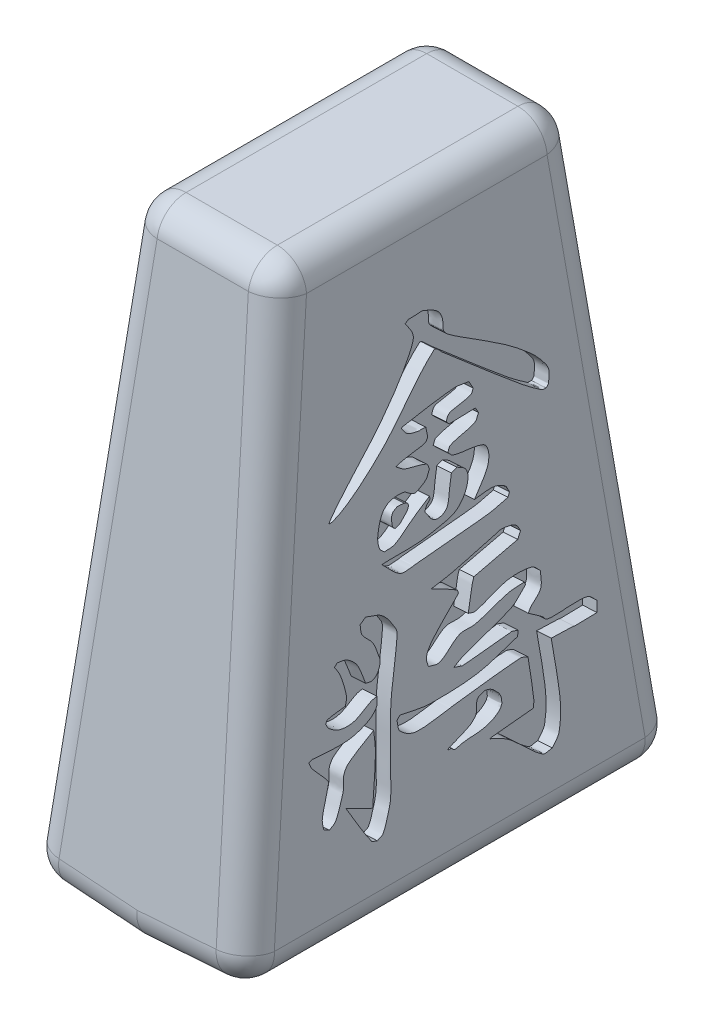
SolidWorks part; units mm, degrees
ref_plane "Płaszczyzna przednia" through (0, 0, 0) normal (0, 0, 1) x (1, 0, 0)
ref_plane "Płaszczyzna górna" through (0, 0, 0) normal (0, 1, 0) x (1, 0, 0)
ref_plane "Płaszczyzna prawa" through (0, 0, 0) normal (1, 0, 0) x (0, 0, -1)
sketch "Szkic1" plane through (0, 0, 0) normal (0, 0, 1) x (1, 0, 0)
  line L0 (0, 0) -> (0, 40)
  line L1 (3.1225, 40) -> (-3.1225, 40)
  line L2 (-5.1185, 38.1262) -> (-7.3738, 2.4704)
  line L3 (-5.504, 0.3481) -> (0, 0)
  line L4 (5.504, 0.3481) -> (0, 0)
  line L5 (5.1185, 38.1262) -> (7.3738, 2.4704)
  arc A0 (-3.1225, 40) -> (-5.1185, 38.1262) centre (-3.1225, 38) ccw
  arc A1 (-7.3738, 2.4704) -> (-5.504, 0.3481) centre (-5.3777, 2.3441) ccw
  arc A2 (7.3738, 2.4704) -> (5.504, 0.3481) centre (5.3777, 2.3441) cw
  arc A3 (3.1225, 40) -> (5.1185, 38.1262) centre (3.1225, 38) cw
  point P7 (-5, 40)
  point P10 (-7.5, 0.4744)
  point P17 (7.5, 0.4744)
  point P18 (5, 40)
  dimension "D5" = 2
  dimension "D1" = 40
  dimension "D2" = 90
  dimension "D3" = 5
  dimension "D4" = 7.5
extrude "Dodanie-wyciągnięcie1" add sketch "Szkic1" along normal blind 30 contours L2 A1 L3 L0 L1 A0 | A3 L1 L0 L4 A2 L5 region at (-3.1441, 18.7866, 0) region at (3.1441, 18.7866, 0)
ref_plane "Płaszczyzna1" through (5.1225, 0, 0) normal (1, 0, 0) x (0, 0, -1)
ref_plane "Płaszczyzna2" through (15.1225, 0, 0) normal (1, 0, 0) x (0, 0, -1)
sketch "Szkic7" plane through (15.1225, 0, 0) normal (1, 0, 0) x (0, 0, -1)
  line L0 (-25, 40) -> (-5, 40)
  line L1 (-30, 40) -> (0, 40) construction
  line L2 (-5, 40) -> (0, 0)
  line L3 (0, 0) -> (-30, 0)
  line L4 (-30, 0) -> (0, 0) construction
  line L5 (-15, 0) -> (-15, 40)
  line L6 (-25, 40) -> (-30, 0)
  line L8 (0, 0) -> (-30, 0)
  line L9 (0, 0) -> (0, 40)
  line L10 (0, 40) -> (-30, 40)
  line L11 (-30, 0) -> (-30, 40)
  dimension "D1" = 10
  dimension "D2" = 15
  dimension "D3" = 40
extrude "Wytnij-wyciągnięcie11" cut sketch "Szkic7" against normal through all and the other way through all contours L11 L6 L10 | L9 L10 L2 region at (15.1225, 26.6667, 28.3333) region at (15.1225, 26.6667, 1.6667)
fillet "Zaokrąglenie2" radius 2 18 edges at (0, 40, 5) (-4.4914, 39.4582, 4.9323) (-6.2461, 20.2983, 2.5373) (-6.8784, 1.022, 0.1278) (-2.752, 0.1741, 0.0218) (2.752, 0.1741, 0.0218) (6.8784, 1.022, 0.1278) (6.2461, 20.2983, 2.5373) (4.4914, 39.4582, 4.9323) (4.4914, 39.4582, 25.0677) (6.2461, 20.2983, 27.4627) (6.8784, 1.022, 29.8722) (2.752, 0.1741, 29.9782) (-2.752, 0.1741, 29.9782) (-6.8784, 1.022, 29.8722) (-6.2461, 20.2983, 27.4627) (-4.4914, 39.4582, 25.0677) (0, 40, 25)
sketch "Szkic8" plane through (7.5, 0.4744, 0) normal (0.998, 0.0631, 0) x (0, 0, -1)
  line L0 (275.1153, 442.3408) -> (941.782, 442.3408) construction
  line L1 (166.6667, 500) -> (833.3333, 500) construction
  line L2 (226.291, 543.6223) -> (892.9577, 543.6223) construction
  line L3 (200, 714.5) -> (1000, 714.5) construction
  line L4 (-12.7553, 27.571) -> (-12.4913, 27.067)
  line L5 (-14.4113, 26.059) -> (-14.2193, 25.843)
  line L6 (-14.2193, 25.843) -> (-12.4193, 25.891)
  line L7 (-12.4193, 25.891) -> (-12.2273, 25.531)
  line L8 (-10.4513, 20.107) -> (-10.5713, 19.843)
  line L9 (-13.8593, 23.179) -> (-14.2433, 23.035)
  line L10 (-15.7553, 22.267) -> (-15.7793, 22.435)
  line L11 (-15.6833, 25.795) -> (-15.7793, 26.419)
  line L12 (-22.4273, 7.675) -> (-20.6513, 6.835)
  line L13 (-23.6033, 7.003) -> (-23.9873, 7.219)
  line L14 (-22.6913, 15.931) -> (-22.4993, 16.099)
  line L15 (-9.8513, 17.587) -> (-10.0673, 17.179)
  line L16 (-10.0673, 17.179) -> (-13.1153, 16.507)
  line L17 (-5.0273, 11.227) -> (-5.0513, 10.531)
  line L18 (-18.7313, 10.963) -> (-18.5153, 11.155)
  line L19 (-10.4273, 11.755) -> (-10.3553, 12.091)
  line L20 (-9.7073, 14.395) -> (-9.7793, 14.587)
  line L21 (-15.2273, 7.651) -> (-15.4673, 7.651)
  line L22 (-15.4673, 7.651) -> (-15.4193, 7.675)
  line L23 (-15.4193, 7.675) -> (-15.4433, 7.699)
  spline S0 degree 3 poles (-17.4113, 27.115) (-17.3793, 27.139) (-17.3548, 27.1806) (-17.3153, 27.187) (-16.1581, 27.3734) (-15.0033, 27.5926) (-13.8353, 27.691) (-13.4744, 27.7214) (-13.1153, 27.611) (-12.7553, 27.571) knots 0 0 0 0 1 1 1 2 2 2 3 3 3 3
  spline S1 degree 3 poles (-12.4913, 27.067) (-12.5553, 26.971) (-12.5773, 26.8244) (-12.6833, 26.779) (-12.992, 26.6467) (-13.3407, 26.6408) (-13.6673, 26.563) (-13.8448, 26.5207) (-14.0443, 26.5213) (-14.1953, 26.419) (-14.3112, 26.3405) (-14.3393, 26.179) (-14.4113, 26.059) knots 0 0 0 0 1 1 1 2 2 2 3 3 3 4 4 4 4
  spline S2 degree 3 poles (-12.2273, 25.531) (-12.3233, 25.387) (-12.3583, 25.1717) (-12.5153, 25.099) (-13.0438, 24.8541) (-13.6604, 24.8492) (-14.1953, 24.619) (-14.3176, 24.5663) (-14.3393, 24.395) (-14.4113, 24.283) knots 0 0 0 0 1 1 1 2 2 2 3 3 3 3
  spline S3 degree 3 poles (-14.4113, 24.283) (-14.2913, 24.179) (-14.2037, 24.0156) (-14.0513, 23.971) (-13.3948, 23.7787) (-12.6687, 23.8455) (-12.0353, 23.587) (-11.8295, 23.503) (-11.7247, 23.2318) (-11.6993, 23.011) (-11.665, 22.7117) (-11.7326, 22.3924) (-11.8673, 22.123) (-12.1086, 21.6405) (-12.4913, 21.243) (-12.8033, 20.803) knots 0 0 0 0 1 1 1 2 2 2 3 3 3 4 4 4 5 5 5 5
  spline S4 degree 3 poles (-12.8033, 20.803) (-12.3793, 20.835) (-11.9542, 20.9432) (-11.5313, 20.899) (-11.2491, 20.8694) (-10.9681, 20.7548) (-10.7393, 20.587) (-10.5889, 20.4766) (-10.5473, 20.267) (-10.4513, 20.107) knots 0 0 0 0 1 1 1 2 2 2 3 3 3 3
  spline S5 degree 3 poles (-10.5713, 19.843) (-11.0193, 19.747) (-11.4604, 19.6091) (-11.9153, 19.555) (-13.6148, 19.3528) (-15.3239, 19.2406) (-17.0273, 19.075) (-17.0525, 19.0725) (-17.074, 19.051) (-17.0993, 19.051) (-17.4034, 19.051) (-17.7419, 18.934) (-18.0113, 19.075) (-18.4729, 19.3165) (-18.7793, 19.779) (-19.1633, 20.131) knots 0 0 0 0 1 1 1 2 2 2 3 3 3 4 4 4 5 5 5 5
  spline S6 degree 3 poles (-19.1633, 20.131) (-19.1393, 20.139) (-19.1166, 20.1536) (-19.0913, 20.155) (-17.9473, 20.219) (-16.773, 20.0775) (-15.6593, 20.347) (-15.1878, 20.461) (-14.6858, 20.4841) (-14.2433, 20.683) (-13.9537, 20.8132) (-13.7099, 21.0499) (-13.5233, 21.307) (-13.3401, 21.5595) (-13.213, 21.863) (-13.1633, 22.171) (-13.1296, 22.3801) (-13.163, 22.6207) (-13.2833, 22.795) (-13.4144, 22.9849) (-13.6673, 23.051) (-13.8593, 23.179) knots 0 0 0 0 1 1 1 2 2 2 3 3 3 4 4 4 5 5 5 6 6 6 7 7 7 7
  spline S7 degree 3 poles (-14.2433, 23.035) (-14.2993, 22.771) (-14.3528, 22.5064) (-14.4113, 22.243) (-14.4808, 21.9304) (-14.4863, 21.5944) (-14.6273, 21.307) (-14.7049, 21.1488) (-14.8678, 21.0254) (-15.0353, 20.971) (-15.2105, 20.914) (-15.4331, 20.8944) (-15.5873, 20.995) (-15.8354, 21.1567) (-15.9553, 21.459) (-16.1393, 21.691) knots 0 0 0 0 1 1 1 2 2 2 3 3 3 4 4 4 5 5 5 5
  spline S8 degree 3 poles (-16.1393, 21.691) (-16.1073, 21.779) (-16.0953, 21.8771) (-16.0433, 21.955) (-15.9648, 22.0727) (-15.8513, 22.163) (-15.7553, 22.267) knots 0 0 0 0 1 1 1 2 2 2 2
  spline S9 degree 3 poles (-15.7793, 22.435) (-16.1393, 22.219) (-16.5053, 22.0126) (-16.8593, 21.787) (-17.3215, 21.4925) (-17.7327, 21.111) (-18.2273, 20.875) (-18.453, 20.7673) (-18.7233, 20.811) (-18.9713, 20.779) knots 0 0 0 0 1 1 1 2 2 2 3 3 3 3
  spline S10 degree 3 poles (-18.9713, 20.779) (-19.0753, 20.891) (-19.2321, 20.971) (-19.2833, 21.115) (-19.3668, 21.3497) (-19.3937, 21.6128) (-19.3553, 21.859) (-19.2957, 22.2414) (-19.196, 22.632) (-18.9953, 22.963) (-18.8626, 23.182) (-18.6397, 23.3664) (-18.3953, 23.443) (-18.0746, 23.5435) (-17.7164, 23.5355) (-17.3873, 23.467) (-17.3472, 23.4586) (-16.8601, 22.9609) (-16.5953, 23.107) (-16.3851, 23.223) (-16.1457, 23.3018) (-15.9713, 23.467) (-15.8309, 23.6001) (-15.7793, 23.803) (-15.6833, 23.971) knots 0 0 0 0 1 1 1 2 2 2 3 3 3 4 4 4 5 5 5 6 6 6 7 7 7 8 8 8 8
  spline S11 degree 3 poles (-15.6833, 23.971) (-15.7473, 24.091) (-15.7526, 24.2723) (-15.8753, 24.331) (-16.3343, 24.5505) (-16.8689, 24.5692) (-17.3393, 24.763) (-17.5569, 24.8526) (-17.7233, 25.035) (-17.9153, 25.171) knots 0 0 0 0 1 1 1 2 2 2 3 3 3 3
  spline S12 degree 3 poles (-17.9153, 25.171) (-17.6889, 25.2464) (-17.454, 25.2955) (-17.2193, 25.339) (-16.7809, 25.4202) (-16.3267, 25.4281) (-15.8993, 25.555) (-15.7962, 25.5856) (-15.7553, 25.715) (-15.6833, 25.795) knots 0 0 0 0 1 1 1 2 2 2 3 3 3 3
  spline S13 degree 3 poles (-15.7793, 26.419) (-15.8993, 26.427) (-16.0191, 26.443) (-16.1393, 26.443) (-16.1646, 26.443) (-16.1866, 26.4135) (-16.2113, 26.419) (-16.4785, 26.4783) (-16.7666, 26.4977) (-17.0033, 26.635) (-17.185, 26.7403) (-17.2753, 26.955) (-17.4113, 27.115) knots 0 0 0 0 1 1 1 2 2 2 3 3 3 4 4 4 4
  spline S14 degree 3 poles (-17.4833, 22.867) (-17.4721, 22.8658) (-17.4697, 22.8474) (-17.4593, 22.843) (-17.4128, 22.823) (-17.3568, 22.824) (-17.3153, 22.795) (-17.2734, 22.7656) (-17.2301, 22.7251) (-17.2193, 22.675) (-17.1879, 22.5284) (-17.2912, 22.3682) (-17.3873, 22.267) (-17.5004, 22.148) (-17.625, 22.0404) (-17.7473, 21.931) (-17.8735, 21.8181) (-18.0161, 21.7662) (-18.1793, 21.739) knots 6 6 6 6 7 7 7 8 8 8 9 9 9 10 10 10 11 11 11 12 12 12 12
  spline S15 degree 3 poles (-18.1793, 21.739) (-18.2273, 21.787) (-18.293, 21.8223) (-18.3233, 21.883) (-18.3598, 21.9559) (-18.3653, 22.0416) (-18.3713, 22.123) (-18.3914, 22.3942) (-18.4086, 22.4837) (-18.2993, 22.675) (-18.2528, 22.7565) (-18.1338, 22.8091) (-18.0593, 22.843) (-18.0201, 22.8608) (-17.9824, 22.8892) (-17.9393, 22.891) (-17.7873, 22.8973) (-17.6348, 22.8821) (-17.4833, 22.867) knots 0 0 0 0 1 1 1 2 2 2 3 3 3 4 4 4 5 5 5 6 6 6 6
  spline S16 degree 3 poles (-20.8433, 17.491) (-20.7313, 17.563) (-20.6237, 17.6423) (-20.5073, 17.707) (-20.4785, 17.723) (-20.4423, 17.7423) (-20.4113, 17.731) (-20.0445, 17.5962) (-19.635, 17.521) (-19.3313, 17.275) (-18.9807, 16.991) (-18.7431, 16.5845) (-18.5153, 16.195) (-18.433, 16.0541) (-18.3972, 15.8766) (-18.4193, 15.715) (-18.5905, 14.4666) (-18.9329, 13.245) (-19.0913, 11.995) (-19.2294, 10.9053) (-19.2124, 9.8012) (-19.3073, 8.707) (-19.3826, 7.84) (-19.2871, 6.9193) (-19.6193, 6.115) (-19.7617, 5.7703) (-19.8431, 5.3923) (-20.0513, 5.083) (-20.1373, 4.9553) (-20.3233, 4.939) (-20.4593, 4.867) knots 0 0 0 0 1 1 1 2 2 2 3 3 3 4 4 4 5 5 5 6 6 6 7 7 7 8 8 8 9 9 9 10 10 10 10
  spline S17 degree 3 poles (-20.4593, 4.867) (-20.5953, 4.931) (-20.7811, 4.9359) (-20.8673, 5.059) (-21.45, 5.8904) (-21.9073, 6.803) (-22.4273, 7.675) knots 0 0 0 0 1 1 1 2 2 2 2
  spline S18 degree 3 poles (-20.6513, 6.835) (-20.5233, 7.851) (-20.3467, 8.862) (-20.2673, 9.883) (-20.2344, 10.306) (-20.2993, 10.731) (-20.3153, 11.155) knots 0 0 0 0 1 1 1 2 2 2 2
  spline S19 degree 3 poles (-20.3153, 11.155) (-20.8993, 10.819) (-21.5203, 10.5403) (-22.0673, 10.147) (-22.244, 10.0199) (-22.3815, 9.8251) (-22.4513, 9.619) (-22.5628, 9.29) (-22.4598, 8.9068) (-22.5953, 8.587) (-22.7757, 8.1614) (-22.8992, 7.7049) (-23.1473, 7.315) (-23.2462, 7.1596) (-23.4513, 7.107) (-23.6033, 7.003) knots 0 0 0 0 1 1 1 2 2 2 3 3 3 4 4 4 5 5 5 5
  spline S20 degree 3 poles (-23.9873, 7.219) (-24.0033, 7.435) (-24.0786, 7.6547) (-24.0353, 7.867) (-23.9084, 8.4894) (-23.6537, 9.079) (-23.4833, 9.691) (-23.4765, 9.7153) (-23.4928, 9.7423) (-23.5073, 9.763) (-23.6055, 9.9032) (-23.709, 10.0401) (-23.8193, 10.171) (-24.0532, 10.4483) (-24.3253, 10.6941) (-24.5393, 10.987) (-24.6323, 11.1142) (-24.6673, 11.275) (-24.7313, 11.419) knots 0 0 0 0 1 1 1 2 2 2 3 3 3 4 4 4 5 5 5 6 6 6 6
  spline S21 degree 3 poles (-24.7313, 11.419) (-24.6353, 11.451) (-24.5426, 11.4951) (-24.4433, 11.515) (-24.4185, 11.5199) (-24.3966, 11.492) (-24.3713, 11.491) (-23.6276, 11.46) (-22.881, 11.3555) (-22.1393, 11.419) (-21.6521, 11.4606) (-21.1696, 11.6029) (-20.7233, 11.803) (-20.4588, 11.9216) (-20.2086, 12.1115) (-20.0513, 12.355) (-19.9421, 12.5242) (-20.0033, 12.755) (-19.9793, 12.955) knots 0 0 0 0 1 1 1 2 2 2 3 3 3 4 4 4 5 5 5 6 6 6 6
  spline S22 degree 3 poles (-19.9793, 12.955) (-20.1153, 12.923) (-20.2584, 12.9128) (-20.3873, 12.859) (-20.7967, 12.6879) (-21.1586, 12.3973) (-21.5873, 12.283) (-21.8965, 12.2005) (-22.2364, 12.2075) (-22.5473, 12.283) (-22.8154, 12.3481) (-23.0541, 12.516) (-23.2673, 12.691) (-23.3755, 12.7797) (-23.4113, 12.931) (-23.4833, 13.051) knots 0 0 0 0 1 1 1 2 2 2 3 3 3 4 4 4 5 5 5 5
  spline S23 degree 3 poles (-23.4833, 13.051) (-23.4273, 13.115) (-23.3976, 13.2213) (-23.3153, 13.243) (-22.9247, 13.3458) (-22.5153, 13.355) (-22.1153, 13.411) knots 0 0 0 0 1 1 1 2 2 2 2
  spline S24 degree 3 poles (-22.1153, 13.411) (-22.0753, 13.579) (-21.9755, 13.7434) (-21.9953, 13.915) (-22.0492, 14.3814) (-22.1781, 14.8391) (-22.3313, 15.283) (-22.412, 15.5165) (-22.5713, 15.715) (-22.6913, 15.931) knots 0 0 0 0 1 1 1 2 2 2 3 3 3 3
  spline S25 degree 3 poles (-22.4993, 16.099) (-22.2833, 16.051) (-22.0426, 16.0663) (-21.8513, 15.955) (-21.5871, 15.8013) (-21.339, 15.5916) (-21.1793, 15.331) (-20.9372, 14.9357) (-20.8433, 14.467) (-20.6753, 14.035) knots 0 0 0 0 1 1 1 2 2 2 3 3 3 3
  spline S26 degree 3 poles (-20.6753, 14.035) (-20.5153, 14.019) (-20.347, 13.9337) (-20.1953, 13.987) (-20.0242, 14.0471) (-19.8699, 14.1855) (-19.7873, 14.347) (-19.6233, 14.6677) (-19.5998, 14.8449) (-19.6913, 15.091) (-19.8105, 15.4113) (-19.8767, 15.7572) (-20.0513, 16.051) (-20.234, 16.3583) (-20.575, 16.5537) (-20.7473, 16.867) (-20.8488, 17.0514) (-20.8113, 17.283) (-20.8433, 17.491) knots 0 0 0 0 1 1 1 2 2 2 3 3 3 4 4 4 5 5 5 6 6 6 6
  spline S27 degree 3 poles (-15.9953, 17.203) (-15.5153, 17.283) (-15.0306, 17.3385) (-14.5553, 17.443) (-13.5737, 17.6587) (-12.6033, 17.9229) (-11.6273, 18.163) (-11.5953, 18.1709) (-11.5636, 18.18) (-11.5313, 18.187) (-11.3795, 18.22) (-11.2301, 18.2968) (-11.0753, 18.283) (-10.7719, 18.2559) (-10.4521, 18.2176) (-10.1873, 18.067) (-10.0176, 17.9704) (-9.9633, 17.747) (-9.8513, 17.587) knots 0 0 0 0 1 1 1 2 2 2 3 3 3 4 4 4 5 5 5 6 6 6 6
  spline S28 degree 3 poles (-13.1153, 16.507) (-13.1633, 16.379) (-13.2238, 16.255) (-13.2593, 16.123) (-13.392, 15.6302) (-13.4993, 15.131) (-13.6193, 14.635) knots 0 0 0 0 1 1 1 2 2 2 2
  spline S29 degree 3 poles (-13.6193, 14.635) (-13.4513, 14.603) (-13.2823, 14.502) (-13.1153, 14.539) (-12.3619, 14.7057) (-11.6684, 15.1073) (-10.9073, 15.235) (-10.3627, 15.3263) (-9.7887, 15.3141) (-9.2513, 15.187) (-9.0081, 15.1294) (-8.8673, 14.867) (-8.6753, 14.707) knots 0 0 0 0 1 1 1 2 2 2 3 3 3 4 4 4 4
  spline S30 degree 3 poles (-8.6753, 14.707) (-8.6913, 14.371) (-8.5887, 14.0073) (-8.7233, 13.699) (-8.8546, 13.3983) (-9.1963, 13.2436) (-9.4193, 13.003) (-9.5009, 12.915) (-9.5633, 12.811) (-9.6353, 12.715) knots 0 0 0 0 1 1 1 2 2 2 3 3 3 3
  spline S31 degree 3 poles (-9.6353, 12.715) (-9.3153, 12.491) (-8.9856, 12.2803) (-8.6753, 12.043) (-8.5765, 11.9674) (-8.5333, 11.8038) (-8.4113, 11.779) (-8.035, 11.7024) (-7.6434, 11.755) (-7.2593, 11.755) (-7.2263, 11.755) (-7.1963, 11.7795) (-7.1633, 11.779) (-6.6591, 11.7715) (-6.1395, 11.8571) (-5.6513, 11.731) (-5.3925, 11.6641) (-5.2353, 11.395) (-5.0273, 11.227) knots 0 0 0 0 1 1 1 2 2 2 3 3 3 4 4 4 5 5 5 6 6 6 6
  spline S32 degree 3 poles (-5.0513, 10.531) (-5.5633, 10.523) (-6.0753, 10.507) (-6.5873, 10.507) (-6.6203, 10.507) (-6.6504, 10.5295) (-6.6833, 10.531) (-7.1871, 10.5535) (-7.6913, 10.563) (-8.1953, 10.579) knots 0 0 0 0 1 1 1 2 2 2 3 3 3 3
  spline S33 degree 3 poles (-8.1953, 10.579) (-8.0673, 9.339) (-7.8549, 8.1048) (-7.8113, 6.859) (-7.7905, 6.2639) (-7.8405, 5.6557) (-8.0033, 5.083) (-8.0799, 4.8136) (-8.3393, 4.635) (-8.5073, 4.411) knots 0 0 0 0 1 1 1 2 2 2 3 3 3 3
  spline S34 degree 3 poles (-8.5073, 4.411) (-8.7313, 4.403) (-8.9919, 4.2641) (-9.1793, 4.387) (-9.9856, 4.9155) (-10.5889, 5.7089) (-11.3633, 6.283) (-11.7399, 6.5621) (-12.1953, 6.715) (-12.6113, 6.931) knots 0 0 0 0 1 1 1 2 2 2 3 3 3 3
  spline S35 degree 3 poles (-12.6113, 6.931) (-12.5473, 6.947) (-12.4849, 6.9721) (-12.4193, 6.979) (-11.4923, 7.0762) (-10.5633, 7.155) (-9.6353, 7.243) knots 0 0 0 0 1 1 1 2 2 2 2
  spline S36 degree 3 poles (-9.6353, 7.243) (-9.6113, 7.411) (-9.554, 7.5775) (-9.5633, 7.747) (-9.6102, 8.5974) (-9.7233, 9.443) (-9.8033, 10.291) knots 0 0 0 0 1 1 1 2 2 2 2
  spline S37 degree 3 poles (-9.8033, 10.291) (-9.9873, 10.347) (-10.1634, 10.4712) (-10.3553, 10.459) (-11.9371, 10.3583) (-13.5078, 10.1274) (-15.0833, 9.955) (-15.1161, 9.9514) (-15.1465, 9.9342) (-15.1793, 9.931) (-15.9629, 9.8542) (-16.7479, 9.6372) (-17.5313, 9.715) (-17.9195, 9.7535) (-18.2929, 9.9858) (-18.5633, 10.267) (-18.7288, 10.439) (-18.6753, 10.731) (-18.7313, 10.963) knots 0 0 0 0 1 1 1 2 2 2 3 3 3 4 4 4 5 5 5 6 6 6 6
  spline S38 degree 3 poles (-18.5153, 11.155) (-17.7873, 11.043) (-17.0679, 10.8133) (-16.3313, 10.819) (-14.9327, 10.8297) (-13.494, 10.8219) (-12.1553, 11.227) (-11.5789, 11.4014) (-11.0033, 11.579) (-10.4273, 11.755) knots 0 0 0 0 1 1 1 2 2 2 3 3 3 3
  spline S39 degree 3 poles (-10.3553, 12.091) (-10.5073, 12.139) (-10.6556, 12.2011) (-10.8113, 12.235) (-10.8436, 12.242) (-10.8745, 12.2143) (-10.9073, 12.211) (-11.9949, 12.1022) (-13.0824, 11.9923) (-14.1713, 11.899) (-14.2042, 11.8962) (-14.2359, 11.9129) (-14.2673, 11.923) (-14.436, 11.9769) (-14.6033, 12.035) (-14.7713, 12.091) knots 0 0 0 0 1 1 1 2 2 2 3 3 3 4 4 4 5 5 5 5
  spline S40 degree 3 poles (-14.7713, 12.091) (-14.5313, 12.211) (-14.3034, 12.3589) (-14.0513, 12.451) (-12.9654, 12.8476) (-11.8186, 13.0827) (-10.7633, 13.555) (-10.3528, 13.7387) (-10.0593, 14.115) (-9.7073, 14.395) knots 0 0 0 0 1 1 1 2 2 2 3 3 3 3
  spline S41 degree 3 poles (-9.7793, 14.587) (-10.1553, 14.555) (-10.5393, 14.5745) (-10.9073, 14.491) (-11.6725, 14.3173) (-12.3972, 13.9886) (-13.1633, 13.819) (-13.5234, 13.7392) (-13.9238, 13.8811) (-14.2673, 13.747) (-14.7903, 13.5428) (-15.1555, 13.0264) (-15.6833, 12.835) (-15.9269, 12.7466) (-16.1953, 12.915) (-16.4513, 12.955) knots 0 0 0 0 1 1 1 2 2 2 3 3 3 4 4 4 5 5 5 5
  spline S42 degree 3 poles (-16.4513, 12.955) (-16.4833, 13.155) (-16.6021, 13.36) (-16.5473, 13.555) (-16.4657, 13.8456) (-16.2733, 14.1023) (-16.0673, 14.323) (-15.4842, 14.9478) (-14.8193, 15.491) (-14.1953, 16.075) knots 0 0 0 0 1 1 1 2 2 2 3 3 3 3
  spline S43 degree 3 poles (-14.1953, 16.075) (-14.2273, 16.155) (-14.2183, 16.2692) (-14.2913, 16.315) (-14.8341, 16.6551) (-15.4273, 16.907) (-15.9953, 17.203) knots 0 0 0 0 1 1 1 2 2 2 2
  spline S44 degree 3 poles (-15.4433, 7.699) (-15.4353, 7.707) (-15.4297, 7.7185) (-15.4193, 7.723) (-15.3169, 7.7669) (-15.2098, 7.7991) (-15.1073, 7.843) (-15.0969, 7.8474) (-15.094, 7.8631) (-15.0833, 7.867) (-15.0048, 7.8955) (-14.9218, 7.9104) (-14.8433, 7.939) (-14.8327, 7.9428) (-14.83, 7.9591) (-14.8193, 7.963) (-14.7408, 7.9915) (-14.6578, 8.0064) (-14.5793, 8.035) (-14.5687, 8.0388) (-14.5659, 8.055) (-14.5553, 8.059) (-14.5008, 8.0794) (-14.4419, 8.0865) (-14.3873, 8.107) (-14.3767, 8.1109) (-14.3738, 8.1266) (-14.3633, 8.131) (-14.2673, 8.171) (-14.1666, 8.2012) (-14.0753, 8.251) (-13.9968, 8.2938) (-13.9139, 8.3281) (-13.8353, 8.371) (-13.7904, 8.3955) (-13.753, 8.4322) (-13.7153, 8.467) (-13.5955, 8.5776) (-13.4561, 8.6782) (-13.4273, 8.851) (-13.3566, 9.2751) (-13.431, 9.2737) (-13.3313, 9.523) (-13.3271, 9.5335) (-13.3153, 9.539) (-13.3073, 9.547) (-13.2673, 9.587) (-13.2364, 9.6389) (-13.1873, 9.667) (-13.1214, 9.7046) (-13.0441, 9.7176) (-12.9713, 9.739) (-12.908, 9.7576) (-12.8453, 9.787) (-12.7793, 9.787) (-12.6037, 9.787) (-12.333, 9.6766) (-12.2033, 9.547) (-12.0239, 9.3675) (-11.8348, 9.2159) (-11.7473, 8.971) (-11.6959, 8.827) (-11.6993, 8.6678) (-11.6993, 8.515) (-11.6993, 8.5037) (-11.7183, 8.5011) (-11.7233, 8.491) (-11.8253, 8.2871) (-11.7475, 8.3708) (-11.8193, 8.299) (-11.8513, 8.267) (-11.8813, 8.2328) (-11.9153, 8.203) (-12.2545, 7.9062) (-12.7259, 7.7597) (-13.1633, 7.699) (-13.3305, 7.6758) (-13.4987, 7.6569) (-13.6673, 7.651) (-15.1852, 7.5974) (-14.8419, 7.2655) (-15.2273, 7.651) knots 0 0 0 0 1 1 1 2 2 2 3 3 3 4 4 4 5 5 5 6 6 6 7 7 7 8 8 8 9 9 9 10 10 10 11 11 11 12 12 12 13 13 13 14 14 14 15 15 15 16 16 16 17 17 17 18 18 18 19 19 19 20 20 20 21 21 21 22 22 22 23 23 23 24 24 24 25 25 25 26 26 26 27 27 27 27
  spline S45 degree 3 poles (-7.6673, 24.739) (-7.7714, 24.7234) (-7.8913, 24.7293) (-7.9793, 24.787) (-8.5723, 25.1752) (-9.1357, 25.609) (-9.6833, 26.059) (-11.2885, 27.3777) (-12.8353, 28.7661) (-14.4353, 30.091) (-14.6045, 30.2311) (-14.8158, 30.5882) (-14.9873, 30.451) (-16.2641, 29.4296) (-17.2255, 28.0653) (-18.3953, 26.923) (-18.9311, 26.3998) (-19.5092, 25.92) (-20.0993, 25.459) (-20.5347, 25.1188) (-20.9918, 24.8042) (-21.4673, 24.523) (-21.7386, 24.3625) (-22.0323, 24.2386) (-22.3313, 24.139) (-22.4001, 24.1161) (-22.5892, 24.1039) (-22.5473, 24.163) (-22.213, 24.6345) (-21.7942, 25.0407) (-21.3953, 25.459) (-20.6419, 26.2491) (-19.8342, 26.9869) (-19.0913, 27.787) (-18.5853, 28.3319) (-18.1063, 28.9027) (-17.6513, 29.491) (-17.3133, 29.928) (-17.0004, 30.3856) (-16.7153, 30.859) (-16.551, 31.1318) (-16.3926, 31.4161) (-16.3073, 31.723) (-16.2686, 31.8626) (-16.2986, 32.0217) (-16.3553, 32.155) (-16.4623, 32.4062) (-16.6433, 32.619) (-16.7873, 32.851) knots 16 16 16 16 17 17 17 18 18 18 19 19 19 20 20 20 21 21 21 22 22 22 23 23 23 24 24 24 25 25 25 26 26 26 27 27 27 28 28 28 29 29 29 30 30 30 31 31 31 32 32 32 32
  spline S46 degree 3 poles (-16.7873, 32.851) (-16.7233, 32.891) (-16.6601, 32.9321) (-16.5953, 32.971) (-16.58, 32.9802) (-16.5652, 32.9953) (-16.5473, 32.995) (-15.7075, 32.9785) (-15.7061, 33.121) (-15.3233, 32.923) (-15.1072, 32.8112) (-14.8677, 32.736) (-14.6753, 32.587) (-14.54, 32.4821) (-14.4348, 32.3345) (-14.3633, 32.179) (-14.2952, 32.0307) (-14.2871, 31.8609) (-14.2673, 31.699) (-14.247, 31.532) (-14.3215, 31.3439) (-14.2433, 31.195) (-14.1407, 30.9996) (-13.9436, 30.8662) (-13.7633, 30.739) (-13.2611, 30.3844) (-12.7205, 30.0874) (-12.2033, 29.755) (-11.4885, 29.2954) (-10.7595, 28.8561) (-10.0673, 28.363) (-9.5341, 27.9831) (-9.0155, 27.5796) (-8.5313, 27.139) (-8.2129, 26.8492) (-7.9274, 26.5221) (-7.6673, 26.179) (-7.5485, 26.0222) (-7.4327, 25.8455) (-7.4033, 25.651) (-7.3661, 25.4046) (-7.4454, 25.1543) (-7.4753, 24.907) (-7.4775, 24.8892) (-7.4859, 24.8708) (-7.4993, 24.859) (-7.5511, 24.8137) (-7.5993, 24.7492) (-7.6673, 24.739) knots 0 0 0 0 1 1 1 2 2 2 3 3 3 4 4 4 5 5 5 6 6 6 7 7 7 8 8 8 9 9 9 10 10 10 11 11 11 12 12 12 13 13 13 14 14 14 15 15 15 16 16 16 16
extrude "Wytnij-wyciągnięcie12" cut sketch "Szkic8" against normal blind 1 contours S13 L11 S12 S11 S10 S9 L10 S8 S7 L9 S6 S5 L8 S4 S3 S2 L7 L6 L5 S1 L4 S0 S14 S15 | S46 S45 | S43 S42 S41 L20 S40 S39 L19 S38 L18 S37 S36 S35 S34 S33 S32 L17 S31 S30 S29 S28 L16 L15 S27 | S44 L23 L22 L21 | S26 S25 L14 S24 S23 S22 S21 S20 L13 S19 S18 L12 S17 S16 region at (6.0561, 23.3031, 14.953) region at (6.8005, 11.5336, 20.9379) region at (6.3969, 17.914, 10.1321) region at (6.9572, 9.0555, 13.14) region at (5.8331, 26.8278, 19.2193)
